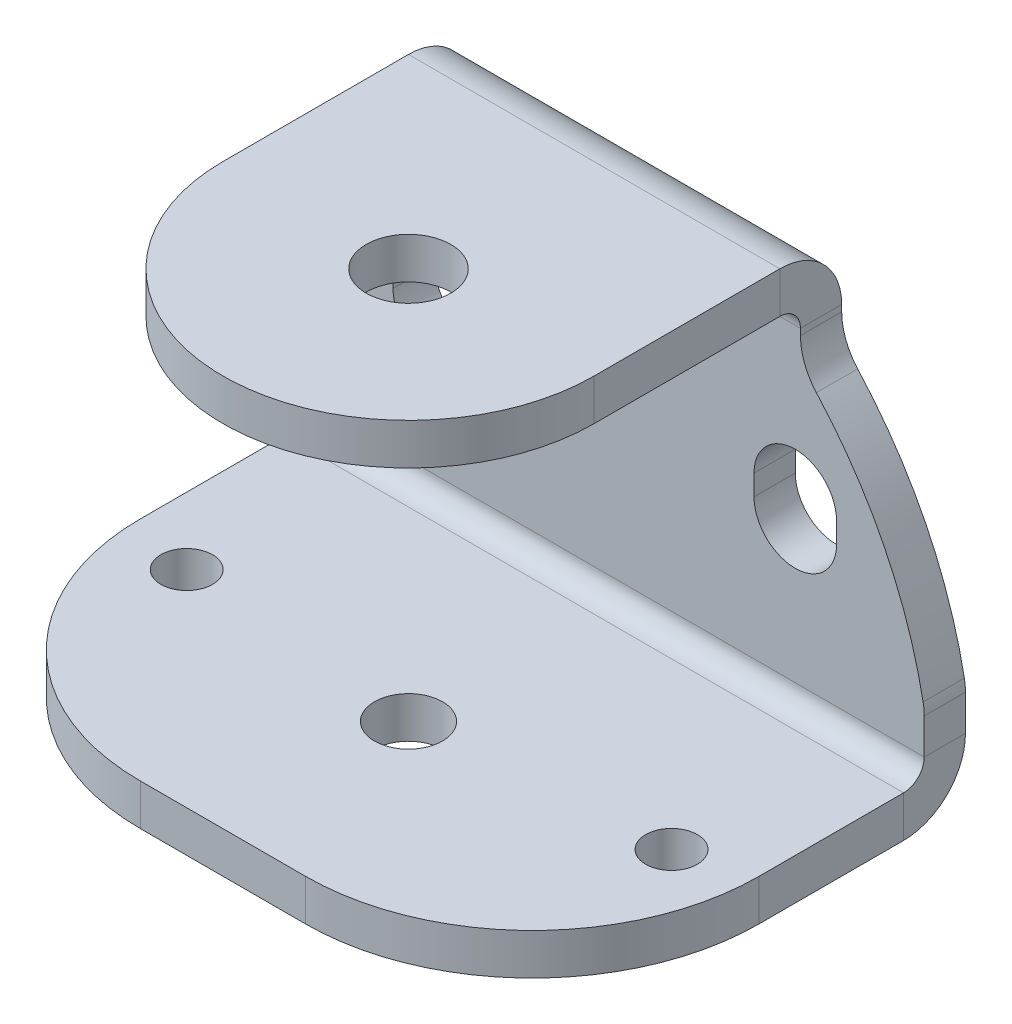
SolidWorks part; units mm, degrees
note: The reader was unsure of these and kept them because the rebuilt part matched: flange length of "Brida de arista1", "Brida de arista2".
material "acero"
ref_plane "Alzado" through (0, 0, 0) normal (0, 0, 1) x (1, 0, 0)
ref_plane "Planta" through (0, 0, 0) normal (0, 1, 0) x (1, 0, 0)
ref_plane "Vista lateral" through (0, 0, 0) normal (1, 0, 0) x (0, 0, -1)
sketch "Croquis1" plane through (0, 0, 0) normal (0, 0, 1) x (1, 0, 0)
  line L0 (0, 0) -> (30, 0)
  line L1 (30, 0) -> (30, 3)
  line L2 (24, 17) -> (6, 17)
  line L3 (6, 17) -> (6, 14.5)
  line L4 (15, 0) -> (15, 17) construction
  line L5 (30, 3) -> (24, 14.5) construction
  line L6 (0.1196, 5.3911) -> (4.2909, 13.386) construction
  line L8 (6, 14.5) -> (0, 3) construction
  line L9 (0, 3) -> (0, 0)
  line L10 (24, 14.5) -> (24, 17)
  arc A0 (0, 3) -> (6, 14.5) centre (21.2027, -0.7471) cw
  arc A1 (30, 3) -> (24, 14.5) centre (8.7973, -0.7471) ccw
  dimension "D1" = 30
  dimension "D2" = 17
  dimension "D3" = 18
  dimension "D4" = 3
  dimension "D5" = 2.5
  dimension "D6" = 1
base flange "Brida base1" sketch "Croquis1" thickness 2 reverse thickness direction no parameters "D1"=0.7366
fillet "Redondeo3mm" radius 3 4 edges at (24, 14.5, -1) (6, 14.5, -1) (30, 3, -1) (0, 3, -1)
edge flange "Brida de arista1" sketch "Croquis8" flange angle 90 flange length 19 flange position material outside bend radius 1 thickness 2 relief rectangular parameters "D6"=10
sketch "Croquis8" plane through (0, 0, 0) normal (0, -1, 0) x (1, 0, 0)
  line L0 (0, 0) -> (30, 0) construction
  line L1 (0, 0) -> (30, 0)
  line L2 (0, 0) -> (0, 19)
  line L3 (0, 19) -> (30, 19)
  line L4 (30, 19) -> (30, 0)
  dimension "D1" = 19
bend "Pliegue de arista5" bend radius 1 bend angle 90 parameters "D5"=1
edge flange "Brida de arista2" sketch "Croquis11" flange angle 90 flange length 10 flange position material outside bend radius 1 thickness 2 relief rectangular parameters "D6"=10
sketch "Croquis11" plane through (0, 17, 0) normal (0, 1, 0) x (-1, 0, 0)
  line L0 (-24, 0) -> (-6, 0) construction
  line L1 (-24, 0) -> (-6, 0)
  line L2 (-24, 0) -> (-24, 10)
  line L4 (-6, 10) -> (-6, 0)
  arc A0 (-6, 10) -> (-24, 10) centre (-15, 10) ccw
bend "Pliegue de arista2" bend radius 1 bend angle 90 parameters "D5"=2
sketch "Croquis26" plane through (0, 0, -2) normal (0, 0, -1) x (-1, 0, 0)
  line L0 (-15, 16) -> (-15, 1) construction
  line L1 (-24, 16) -> (-6, 16) construction
  line L2 (-6.25, 8.3) -> (-15, 8.3) construction
  line L3 (-30, 1) -> (0, 1) construction
  line L4 (-30, 0) -> (0, 0) construction
  line L5 (-6.25, 7.8) -> (-6.25, 8.8) construction
  line L6 (-8.25, 7.8) -> (-8.25, 8.8)
  line L7 (-4.25, 7.8) -> (-4.25, 8.8)
  line L8 (-23.75, 7.8) -> (-23.75, 8.8) construction
  line L9 (-25.75, 7.8) -> (-25.75, 8.8)
  line L10 (-21.75, 7.8) -> (-21.75, 8.8)
  arc A0 (-8.25, 7.8) -> (-4.25, 7.8) centre (-6.25, 7.8) ccw
  circle A1 centre (-6.25, 8.3) radius 2 construction
  circle A2 centre (-23.75, 8.3) radius 2 construction
  arc A3 (-4.25, 8.8) -> (-8.25, 8.8) centre (-6.25, 8.8) ccw
  arc A4 (-25.75, 7.8) -> (-21.75, 7.8) centre (-23.75, 7.8) ccw
  arc A5 (-21.75, 8.8) -> (-25.75, 8.8) centre (-23.75, 8.8) ccw
  point P15 (-6.25, 8.3)
  point P21 (-23.75, 8.3)
  dimension "D1" = 4
  dimension "D3" = 8.3
  dimension "D2" = 17.5
  dimension "D4" = 0.5
  dimension "D5" = 0.5
extrude "Cortar-Extruir6" cut sketch "Croquis26" against normal up to next normal cut yes
fillet "Redondeo11mm" radius 11 2 edges at (0, -1, 19) (30, -1, 19)
hole_wizard "Taladro roscado M32" positions "Croquis33" profile "Croquis32" tap size "M3" standard "Iso"
sketch "Croquis33" plane through (0, 0, 0) normal (0, 1, 0) x (1, 0, 0)
  line L1 (15, 2) -> (15, -22.7453) construction
  line L2 (24, 2) -> (6, 2) construction
  line L3 (30, 0) -> (0, 0) construction
  point P0 (3.25, -9)
  point P2 (26.75, -9)
  dimension "D1" = 9
  dimension "D2" = 11.75
sketch "Croquis32" plane through (3.25, 0, 9) normal (1, 0, 0) x (0, 0, 1)
  line L0 (0, 0) -> (0, 21.4011)
  line L1 (0, 21.4011) -> (1.25, 20.65)
  line L2 (1.25, 20.65) -> (1.25, 0)
  line L5 (1.25, 0) -> (0, 0)
  line L10 (0, 21.4011) -> (-1.25, 20.65) construction
  line L11 (0, -6.35) -> (0, 107.95) construction
  dimension "Diámetro de perforador para roscar" = 2.5
  dimension "Profundidad de perforador para roscar" = 20.65
  dimension "Ángulo de perforador" = 118
cosmetic thread "Rosca de taladro5"
cosmetic thread "Rosca de taladro6"
hole_wizard "Taladro roscado M52" [suppressed] positions "Croquis35" profile "Croquis34" tap size "M4" standard "ISO"
sketch "Croquis35" plane through (3.7155, 0, 2.6381) normal (0, 1, 0) x (1, 0, 0)
  line L2 (20.2845, 4.6381) -> (2.2845, 4.6381) construction
  line L3 (11.2845, 4.6381) -> (11.2845, -10.5472) construction
  line L4 (26.2845, 2.6381) -> (-3.7155, 2.6381) construction
  point P0 (11.2845, -7.3619)
  dimension "D1" = 10
cosmetic thread "Rosca de taladro7" [suppressed]
sketch "Croquis34" plane through (15, 0, 10) normal (1, 0, 0) x (0, 0, 1)
  line L0 (0, 0) -> (0, 2)
  line L1 (0, 2) -> (1.65, 2)
  line L2 (1.65, 2) -> (1.65, 0)
  line L5 (1.65, 0) -> (0, 0)
  line L11 (0, -6.35) -> (0, 107.95) construction
  dimension "Diámetro de perforador para roscar hasta el siguiente" = 3.3
  dimension "Profundidad de perforador para roscar hasta el siguiente" = 2
sketch "Croquis36" [suppressed] plane through (0, 17, 0) normal (0, 1, 0) x (1, 0, 0)
  circle A0 centre (15, -10) radius 2.05
  circle A1 centre (15, -10) radius 1.65 construction
  dimension "D1" = 4.1
extrude "Cortar-Extruir7" [suppressed] cut sketch "Croquis36" along normal up to next
sketch "Croquis41" plane through (0, 19, 0) normal (0, 1, 0) x (1, 0, 0)
  line L0 (15, 2) -> (15, -19) construction
  line L1 (6, 2) -> (24, 2) construction
  circle A0 centre (15, -10) radius 2.05
  arc A1 (6, -10) -> (24, -10) centre (15, -10) ccw construction
  dimension "D2" = 4.1
  dimension "D1" = 12
extrude "Cortar-Extruir9" cut sketch "Croquis41" against normal up to surface (2 mm away) normal cut yes up to face at (15, 17, 7.75)
sketch "Posición roscado" plane through (0, 0, 0) normal (0, 1, 0) x (1, 0, 0)
  line L0 (15, 2) -> (15, -16.7473) construction
  line L1 (6, 2) -> (24, 2) construction
  point P0 (15, -10)
  dimension "D1" = 12
hole_wizard "Taladro roscado M41" positions "Croquis3D1" profile "Croquis43" tap size "M4" standard "ISO" end condition through all
sketch3d "Croquis3D1"
  point P0 (15, 0, 10)
sketch "Croquis43" plane through (15, 0, 10) normal (1, 0, 0) x (0, 0, 1)
  line L0 (0, 0) -> (0, 2)
  line L1 (0, 2) -> (1.65, 2)
  line L2 (1.65, 2) -> (1.65, 0)
  line L5 (1.65, 0) -> (0, 0)
  line L11 (0, -6.35) -> (0, 107.95) construction
  dimension "Diámetro de perforador para roscar hasta el siguiente" = 3.3
  dimension "Profundidad de perforador para roscar hasta el siguiente" = 2
cosmetic thread "Rosca de taladro8"
sketch "Líneas de pliegue1" [suppressed] plane through (0, 0, 0) normal (0, 1, 0) x (1, 0, 0)
sketch "Cuadro delimitador1" [suppressed] plane through (0, 0, 0) normal (0, 1, 0) x (1, 0, 0)
sheet metal parameters "Chapa metálica4" thickness 2 parameters "D1"=0.7366
flat pattern "Chapa desplegada4" [suppressed]
sketch "Líneas de pliegue2" plane through (0, 0, 0) normal (0, 1, 0) x (1, 0, 0)
sketch "Cuadro delimitador2" [suppressed] plane through (0, 0, 0) normal (0, 1, 0) x (1, 0, 0)
sheet metal parameters "Chapa metálica5" thickness 2 parameters "D1"=0.7366
flat pattern "Chapa desplegada4" [suppressed]
sketch "Líneas de pliegue2" plane through (0, 0, 0) normal (0, 1, 0) x (1, 0, 0)
sketch "Cuadro delimitador2" [suppressed] plane through (0, 0, 0) normal (0, 1, 0) x (1, 0, 0)
bend of the flat pattern "Aplanar-<Pliegue de arista5>1"
sheet metal parameters "Chapa metálica6" thickness 2 parameters "D1"=0.7366
flat pattern "Chapa desplegada4" [suppressed]
sketch "Líneas de pliegue2" plane through (0, 0, 0) normal (0, 1, 0) x (1, 0, 0)
sketch "Cuadro delimitador2" [suppressed] plane through (0, 0, 0) normal (0, 1, 0) x (1, 0, 0)
bend of the flat pattern "Aplanar-<Pliegue de arista2>1"
bend of the flat pattern "Aplanar-<Pliegue de arista5>2"
sheet metal parameters "Chapa metálica17" thickness 2 parameters "D1"=0.7366
flat pattern "Chapa desplegada4" [suppressed]
sketch "Líneas de pliegue3" plane through (0, 0, 0) normal (0, 1, 0) x (1, 0, 0)
sketch "Cuadro delimitador3" [suppressed] plane through (0, 0, 0) normal (0, 1, 0) x (1, 0, 0)
bend of the flat pattern "Aplanar-<Pliegue de arista5>6"
bend of the flat pattern "Aplanar-<Pliegue de arista2>2"
sheet metal parameters "Chapa metálica(19)" thickness 2 parameters "D1"=0.7366
flat pattern "Chapa desplegada4"
sketch "Líneas de pliegue3" plane through (0, 0, 0) normal (0, 0, 1) x (1, 0, 0)
sketch3d "Cuadro delimitador3" [suppressed]
  line L0 (30, -18.427, 0) -> (30, 36.427, 0) construction
  line L1 (0, -18.427, 0) -> (0, 36.427, 0) construction
  line L2 (30, -18.427, 0) -> (0, -18.427, 0) construction
  line L3 (30, 36.427, 0) -> (0, 36.427, 0) construction
bend of the flat pattern "Aplanar-<Pliegue de arista2>3"
bend of the flat pattern "Aplanar-<Pliegue de arista5>7"
sheet metal parameters "Chapa metálica(20)" thickness 2 parameters "D1"=0.7366
flat pattern "Chapa desplegada4"
sketch "Líneas de pliegue3" plane through (0, 0, 0) normal (0, 0, 1) x (1, 0, 0)
sketch3d "Cuadro delimitador3" [suppressed]
  line L0 (30, -18.427, 0) -> (30, 36.427, 0) construction
  line L1 (0, -18.427, 0) -> (0, 36.427, 0) construction
  line L2 (30, -18.427, 0) -> (0, -18.427, 0) construction
  line L3 (30, 36.427, 0) -> (0, 36.427, 0) construction
bend of the flat pattern "Aplanar-<Pliegue de arista2>3"
bend of the flat pattern "Aplanar-<Pliegue de arista5>7"
sheet metal parameters "Chapa metálica(21)" thickness 2 parameters "D1"=0.7366
flat pattern "Chapa desplegada4"
sketch "Líneas de pliegue3" plane through (0, 0, 0) normal (0, 0, 1) x (1, 0, 0)
  line L0 (24, 17.3562) -> (6, 17.3562) construction
  line L1 (0, -0.3562) -> (30, -0.3562) construction
  line L2 (24, 17.3562) -> (6, 17.3562) construction
  line L3 (0, -0.3562) -> (30, -0.3562) construction
sketch3d "Cuadro delimitador3" [suppressed]
  line L0 (21.2027, 37.4594, 0) -> (21.2027, -18.9653, 0) construction
  line L1 (-8.7973, 37.4594, 0) -> (-8.7973, -18.9653, 0) construction
  line L2 (21.2027, 37.4594, 0) -> (-8.7973, 37.4594, 0) construction
  line L3 (21.2027, -18.9653, 0) -> (-8.7973, -18.9653, 0) construction
bend of the flat pattern "Aplanar-<Pliegue de arista2>3"
bend of the flat pattern "Aplanar-<Pliegue de arista5>7"
sheet metal parameters "Chapa metálica24" thickness 2 parameters "D1"=0.7366
flat pattern "Chapa desplegada4"
sketch "Líneas de pliegue3" plane through (0, 0, 0) normal (0, 0, 1) x (1, 0, 0)
sketch3d "Cuadro delimitador3" [suppressed]
  line L0 (30, -18.427, 0) -> (30, 36.427, 0) construction
  line L1 (0, -18.427, 0) -> (0, 36.427, 0) construction
  line L2 (30, -18.427, 0) -> (0, -18.427, 0) construction
  line L3 (30, 36.427, 0) -> (0, 36.427, 0) construction
bend of the flat pattern "Aplanar-<Pliegue de arista2>3"
bend of the flat pattern "Aplanar-<Pliegue de arista5>7"
sheet metal parameters "Chapa metálica25" thickness 2 parameters "D1"=0.7366
flat pattern "Chapa desplegada4"
sketch "Líneas de pliegue3" plane through (0, 0, 0) normal (0, 0, 1) x (1, 0, 0)
sketch3d "Cuadro delimitador3" [suppressed]
  line L0 (30, -18.427, 0) -> (30, 36.427, 0) construction
  line L1 (0, -18.427, 0) -> (0, 36.427, 0) construction
  line L2 (30, -18.427, 0) -> (0, -18.427, 0) construction
  line L3 (30, 36.427, 0) -> (0, 36.427, 0) construction
bend of the flat pattern "Aplanar-<Pliegue de arista2>3"
bend of the flat pattern "Aplanar-<Pliegue de arista5>7"
